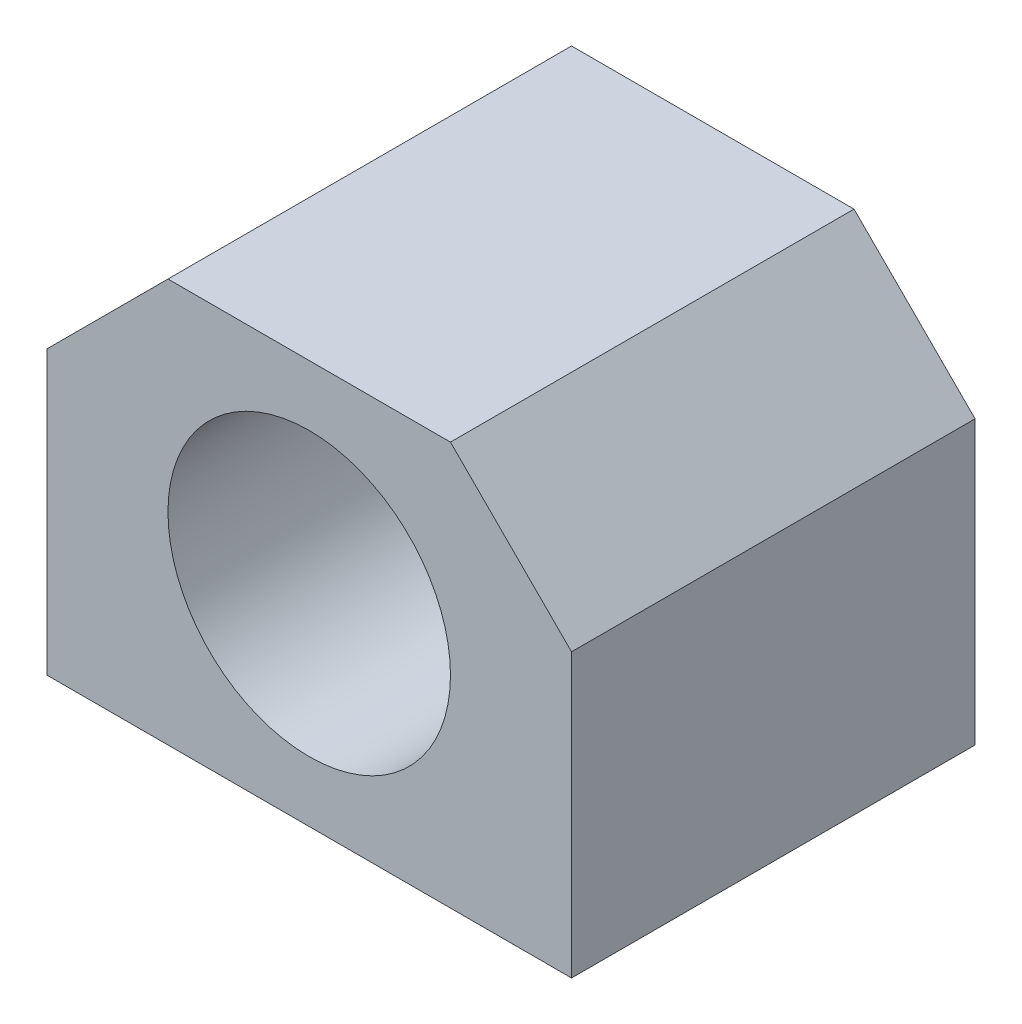
SolidWorks part; units mm, degrees
ref_plane "Front Plane" through (0, 0, 0) normal (0, 0, 1) x (1, 0, 0)
ref_plane "Top Plane" through (0, 0, 0) normal (0, 1, 0) x (1, 0, 0)
ref_plane "Right Plane" through (0, 0, 0) normal (1, 0, 0) x (0, 0, -1)
sketch "Sketch1" plane through (0, 0, 0) normal (0, 0, 1) x (1, 0, 0)
  line L0 (-14, 20) -> (14, 20)
  line L1 (-26, -20) -> (-26, 8)
  line L2 (-26, 8) -> (-14, 20)
  line L3 (-26, -20) -> (26, -20)
  line L4 (0, 20) -> (0, -17.0576) construction
  line L5 (26, -20) -> (26, 8)
  line L6 (26, 8) -> (14, 20)
  line L7 (-26, 8) -> (-26, 20) construction
  line L8 (-26, 20) -> (-14, 20) construction
  line L9 (14, 20) -> (26, 20) construction
  line L10 (26, 20) -> (26, 8) construction
  circle A0 centre (0, 0) radius 14
  dimension "D1" = 28
  dimension "D2" = 52
  dimension "D3" = 20
  dimension "D4" = 40
  dimension "D5" = 45
  dimension "D6" = 12
extrude "Boss-Extrude1" add sketch "Sketch1" along normal blind 40
